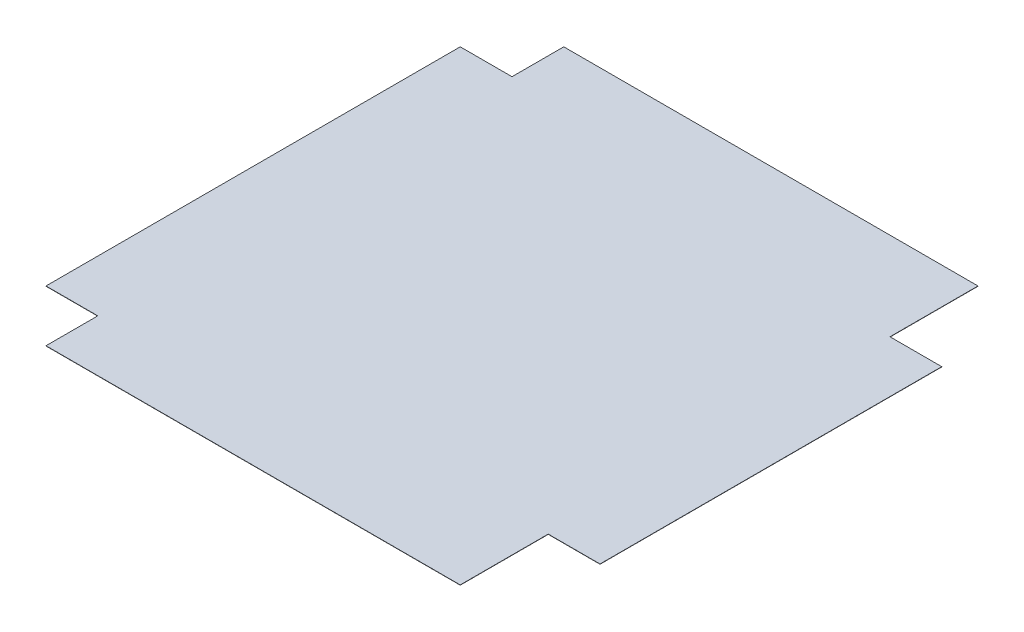
SolidWorks part; units mm, degrees
material "Corrugated Paper"
ref_plane "Front" through (0, 0, 0) normal (0, 0, 1) x (1, 0, 0)
ref_plane "Top" through (0, 0, 0) normal (0, 1, 0) x (1, 0, 0)
ref_plane "Right" through (0, 0, 0) normal (1, 0, 0) x (0, 0, -1)
ref_axis "X" through (-80.9, 0, 0) along (1, 0, 0)
ref_axis "Y" through (0, -50, 0) along (0, 1, 0)
ref_axis "Z" through (0, 0, -80.9) along (0, 0, 1)
sketch "Sketch1" plane through (0, 0, 0) normal (0, 1, 0) x (1, 0, 0)
  line L0 (-80, 100) -> (80, 100)
  line L1 (80, 100) -> (80, 66)
  line L2 (80, 66) -> (100, 66)
  line L3 (100, 66) -> (100, -66)
  line L4 (100, -66) -> (80, -66)
  line L5 (80, -66) -> (80, -100)
  line L6 (80, -100) -> (-80, -100)
  line L7 (-80, -100) -> (-80, -80)
  line L8 (-80, -80) -> (-100, -80)
  line L9 (-100, -80) -> (-100, 80)
  line L10 (-100, 80) -> (-80, 80)
  line L11 (-80, 80) -> (-80, 100)
  line L12 (-100, 0) -> (100, 0) construction
  line L13 (0, 100) -> (0, -100) construction
  point P17 (63.9947, -63.9947)
  point P18 (-68.4625, 68.4625)
  dimension "D1" = 200
  dimension "D2" = 200
  dimension "D3" = 34
  dimension "D4" = 20
extrude "Boss-Extrude1" add sketch "Sketch1" along normal mid plane 0.1
